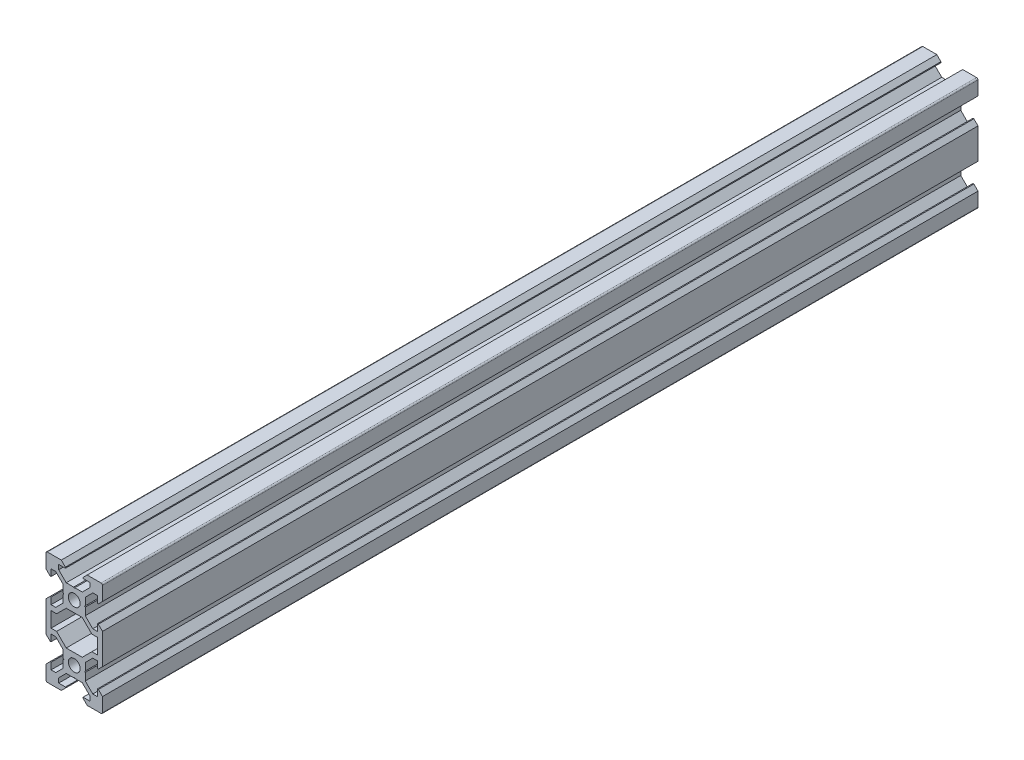
SolidWorks part; units mm, degrees
ref_plane "Plano frontal" through (0, 0, 0) normal (0, 0, 1) x (1, 0, 0)
ref_plane "Plano superior" through (0, 0, 0) normal (0, 1, 0) x (1, 0, 0)
ref_plane "Plano direito" through (0, 0, 0) normal (1, 0, 0) x (0, 0, -1)
sketch "Esboço1" plane through (0, 0, 0) normal (0, 0, 1) x (1, 0, 0)
  line L0 (8.2, -2.7) -> (8.2, 2.7)
  line L1 (8.2, 2.7) -> (6.2393, 2.7)
  line L2 (6.2393, 2.7) -> (2.8393, 6.1)
  line L3 (-2.8393, 6.1) -> (2.8393, 6.1)
  line L4 (-6.2393, 2.7) -> (-2.8393, 6.1)
  line L5 (-8.2, 2.7) -> (-6.2393, 2.7)
  line L6 (-8.2, -2.7) -> (-8.2, 2.7)
  line L7 (-8.2, -2.7) -> (-6.2393, -2.7)
  line L8 (-6.2393, -2.7) -> (-2.8393, -6.1)
  line L9 (-2.8393, -6.1) -> (2.8393, -6.1)
  line L10 (6.2393, -2.7) -> (2.8393, -6.1)
  line L11 (8.2, -2.7) -> (6.2393, -2.7)
  line L12 (3.9, 9.79) -> (3.69, 10)
  line L13 (3.69, 10) -> (3.9, 10.21)
  line L14 (3.9, 10.21) -> (3.9, 12.8393)
  line L15 (3.9, 12.8393) -> (6.5607, 15.5)
  line L16 (6.5607, 15.5) -> (8.2, 15.5)
  line L17 (8.2, 15.5) -> (8.2, 13.125)
  line L18 (8.2, 13.125) -> (8.545, 13.125)
  line L19 (8.545, 13.125) -> (10, 14.58)
  line L20 (10, 14.58) -> (10, 19.5)
  line L21 (9.5, 20) -> (4.58, 20)
  line L22 (4.58, 20) -> (3.125, 18.545)
  line L23 (3.125, 18.545) -> (3.125, 18.2)
  line L24 (3.125, 18.2) -> (5.5, 18.2)
  line L25 (5.5, 18.2) -> (5.5, 16.5607)
  line L26 (5.5, 16.5607) -> (2.8393, 13.9)
  line L27 (2.8393, 13.9) -> (0.21, 13.9)
  line L28 (0.21, 13.9) -> (0, 13.69)
  line L29 (0, 13.69) -> (-0.21, 13.9)
  line L30 (-0.21, 13.9) -> (-2.8393, 13.9)
  line L31 (-2.8393, 13.9) -> (-5.5, 16.5607)
  line L32 (-5.5, 16.5607) -> (-5.5, 18.2)
  line L33 (-5.5, 18.2) -> (-3.125, 18.2)
  line L34 (-3.125, 18.2) -> (-3.125, 18.545)
  line L35 (-3.125, 18.545) -> (-4.58, 20)
  line L36 (-4.58, 20) -> (-9.5, 20)
  line L37 (-10, 19.5) -> (-10, 14.58)
  line L38 (-10, 14.58) -> (-8.545, 13.125)
  line L39 (-8.545, 13.125) -> (-8.2, 13.125)
  line L40 (-8.2, 13.125) -> (-8.2, 15.5)
  line L41 (-8.2, 15.5) -> (-6.5607, 15.5)
  line L42 (-6.5607, 15.5) -> (-3.9, 12.8393)
  line L43 (-3.9, 12.8393) -> (-3.9, 10.21)
  line L44 (-3.9, 10.21) -> (-3.69, 10)
  line L45 (-3.69, 10) -> (-3.9, 9.79)
  line L46 (-3.9, 9.79) -> (-3.9, 7.1607)
  line L47 (-3.9, 7.1607) -> (-6.5607, 4.5)
  line L48 (-6.5607, 4.5) -> (-8.2, 4.5)
  line L49 (-8.2, 4.5) -> (-8.2, 6.875)
  line L50 (-8.2, 6.875) -> (-8.545, 6.875)
  line L51 (-8.545, 6.875) -> (-10, 5.42)
  line L52 (-10, 5.42) -> (-10, -5.42)
  line L53 (-10, -5.42) -> (-8.545, -6.875)
  line L54 (-8.545, -6.875) -> (-8.2, -6.875)
  line L55 (-8.2, -6.875) -> (-8.2, -4.5)
  line L56 (-8.2, -4.5) -> (-6.5607, -4.5)
  line L57 (-6.5607, -4.5) -> (-3.9, -7.1607)
  line L58 (-3.9, -7.1607) -> (-3.9, -9.79)
  line L59 (-3.9, -9.79) -> (-3.69, -10)
  line L60 (-3.69, -10) -> (-3.9, -10.21)
  line L61 (-3.9, -10.21) -> (-3.9, -12.8393)
  line L62 (-3.9, -12.8393) -> (-6.5607, -15.5)
  line L63 (-6.5607, -15.5) -> (-8.2, -15.5)
  line L64 (-8.2, -15.5) -> (-8.2, -13.125)
  line L65 (-8.2, -13.125) -> (-8.545, -13.125)
  line L66 (-8.545, -13.125) -> (-10, -14.58)
  line L67 (-10, -14.58) -> (-10, -19.5)
  line L68 (-9.5, -20) -> (-4.58, -20)
  line L69 (-4.58, -20) -> (-3.125, -18.545)
  line L70 (-3.125, -18.545) -> (-3.125, -18.2)
  line L71 (-3.125, -18.2) -> (-5.5, -18.2)
  line L72 (-5.5, -18.2) -> (-5.5, -16.5607)
  line L73 (-5.5, -16.5607) -> (-2.8393, -13.9)
  line L74 (-2.8393, -13.9) -> (-0.21, -13.9)
  line L75 (-0.21, -13.9) -> (0, -13.69)
  line L76 (0, -13.69) -> (0.21, -13.9)
  line L77 (0.21, -13.9) -> (2.8393, -13.9)
  line L78 (2.8393, -13.9) -> (5.5, -16.5607)
  line L79 (5.5, -16.5607) -> (5.5, -18.2)
  line L80 (5.5, -18.2) -> (3.125, -18.2)
  line L81 (3.125, -18.2) -> (3.125, -18.545)
  line L82 (3.125, -18.545) -> (4.58, -20)
  line L83 (4.58, -20) -> (9.5, -20)
  line L84 (10, -19.5) -> (10, -14.58)
  line L85 (10, -14.58) -> (8.545, -13.125)
  line L86 (8.545, -13.125) -> (8.2, -13.125)
  line L87 (8.2, -13.125) -> (8.2, -15.5)
  line L88 (8.2, -15.5) -> (6.5607, -15.5)
  line L89 (6.5607, -15.5) -> (3.9, -12.8393)
  line L90 (3.9, -12.8393) -> (3.9, -10.21)
  line L91 (3.9, -10.21) -> (3.69, -10)
  line L92 (3.69, -10) -> (3.9, -9.79)
  line L93 (3.9, -9.79) -> (3.9, -7.1607)
  line L94 (3.9, -7.1607) -> (6.5607, -4.5)
  line L95 (6.5607, -4.5) -> (8.2, -4.5)
  line L96 (8.2, -4.5) -> (8.2, -6.875)
  line L97 (8.2, -6.875) -> (8.545, -6.875)
  line L98 (8.545, -6.875) -> (10, -5.42)
  line L99 (10, -5.42) -> (10, 5.42)
  line L100 (10, 5.42) -> (8.545, 6.875)
  line L101 (8.545, 6.875) -> (8.2, 6.875)
  line L102 (8.2, 6.875) -> (8.2, 4.5)
  line L103 (8.2, 4.5) -> (6.5607, 4.5)
  line L104 (6.5607, 4.5) -> (3.9, 7.1607)
  line L105 (3.9, 7.1607) -> (3.9, 9.79)
  circle A0 centre (0, -10) radius 2.1
  circle A1 centre (0, 10) radius 2.1
  arc A2 (10, 19.5) -> (9.5, 20) centre (9.5, 19.5) ccw
  arc A3 (-9.5, 20) -> (-10, 19.5) centre (-9.5, 19.5) ccw
  arc A4 (-10, -19.5) -> (-9.5, -20) centre (-9.5, -19.5) ccw
  arc A5 (9.5, -20) -> (10, -19.5) centre (9.5, -19.5) ccw
extrude "Ressalto-extrusão1" add sketch "Esboço1" along normal blind 310
ref_plane "Plano2" through (0, 0, 0) normal (1, 0, 0) x (0, 0, -1)
ref_plane "Plano3" through (0, 0, 0) normal (0, 1, 0) x (1, 0, 0)
ref_plane "Plano4" through (0, 10, 0) normal (0, 1, 0) x (1, 0, 0)
ref_plane "Plano5" through (0, -10, 0) normal (0, 1, 0) x (1, 0, 0)
